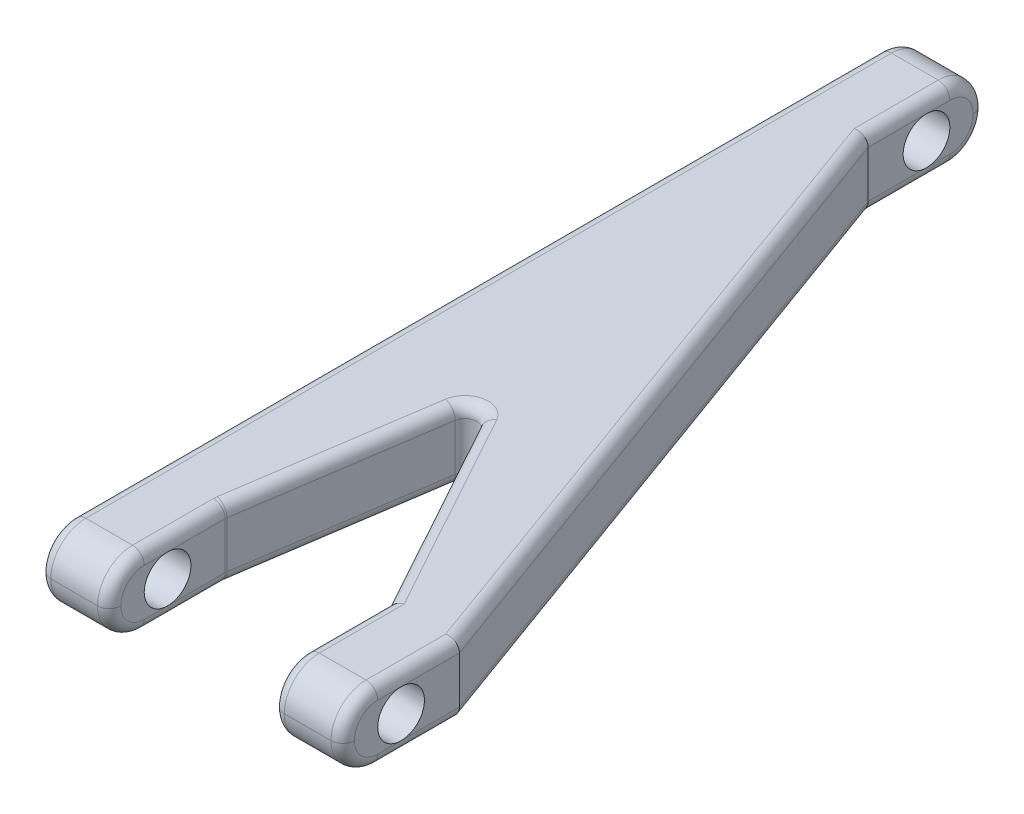
SolidWorks part; units mm, degrees
ref_plane "Front Plane" through (0, 0, 0) normal (0, 0, 1) x (1, 0, 0)
ref_plane "Top Plane" through (0, 0, 0) normal (0, 1, 0) x (1, 0, 0)
ref_plane "Right Plane" through (0, 0, 0) normal (1, 0, 0) x (0, 0, -1)
sketch "Sketch2" plane through (0, 0, 0) normal (0, 1, 0) x (1, 0, 0)
  line L0 (-21, 17.5) -> (-21, -47.5)
  line L1 (-21, -47.5) -> (-15, -47.5)
  line L2 (-15, -47.5) -> (-15, -37.5)
  line L3 (-15, -37.5) -> (-12, -17.5)
  line L4 (-12, -17.5) -> (-1, -37.5)
  line L5 (-1, -37.5) -> (-1, -47.5)
  line L6 (-1, -47.5) -> (5, -47.5)
  line L7 (5, -47.5) -> (5, -37.5)
  line L8 (5, -37.5) -> (-15, 17.5)
  line L9 (-15, 17.5) -> (-15, 27.5)
  line L10 (-15, 27.5) -> (-21, 27.5)
  line L11 (-21, 27.5) -> (-21, 17.5)
  point P2 (-18, -47.5)
  point P13 (2, -47.5)
  dimension "D1" = 10
  dimension "D2" = 6
  dimension "D3" = 10
  dimension "D4" = 10
  dimension "D5" = 6
  dimension "D6" = 6
  dimension "D7" = 20
  dimension "D8" = 20
  dimension "D9" = 3
  dimension "D10" = 75
extrude "Boss-Extrude1" add sketch "Sketch2" along normal blind 6
sketch "Sketch3" plane through (5, 0, 0) normal (1, 0, 0) x (0, 0, -1)
  line L0 (-47.5, 0) -> (-37.5, 0) construction
  line L1 (-47.5, 6) -> (-47.5, 0) construction
  circle A0 centre (-42.5, 3) radius 2
  dimension "D1" = 3
  dimension "D2" = 5
extrude "Cut-Extrude1" cut sketch "Sketch3" against normal through all
sketch "Sketch4" plane through (-15, 0, 0) normal (1, 0, 0) x (0, 0, -1)
  line L0 (27.5, 6) -> (27.5, 0) construction
  line L1 (17.5, 0) -> (27.5, 0) construction
  circle A0 centre (22.5, 3) radius 2
  dimension "D1" = 5
  dimension "D3" = 4
  dimension "D2" = 3
extrude "Cut-Extrude2" cut sketch "Sketch4" against normal through all
fillet "Fillet1" radius 3 6 edges at (-18, 0, -27.5) (-18, 6, -27.5) (2, 0, 47.5) (2, 6, 47.5) (-18, 0, 47.5) (-18, 6, 47.5)
fillet "Fillet2" radius 1 30 edges at (-15, 5.1213, 46.6213) (-15, 0.8787, 46.6213) (-15, 6, 41) (-15, 0, 41) (-6.5, 6, 27.5) (-6.5, 0, 27.5) (5, 0, 41) (5, 0.8787, 46.6213) (5, 5.1213, 46.6213) (-15, 0, -21) (-15, 0.8787, -26.6213) (-15, 5.1213, -26.6213) (-21, 0.8787, -26.6213) (-21, 5.1213, -26.6213) (-21, 5.1213, 46.6213) (-21, 0.8787, 46.6213) (-15, 3, 37.5) (-13.5, 6, 27.5) (-12, 3, 17.5) (-13.5, 0, 27.5) (5, 6, 41) (-15, 6, -21) (-21, 6, 10) (-21, 0, 10) (-5, 0, 10) (-5, 6, 10) (-1, 0, 41) (-1, 0.8787, 46.6213) (-1, 5.1213, 46.6213) (-1, 6, 41)
